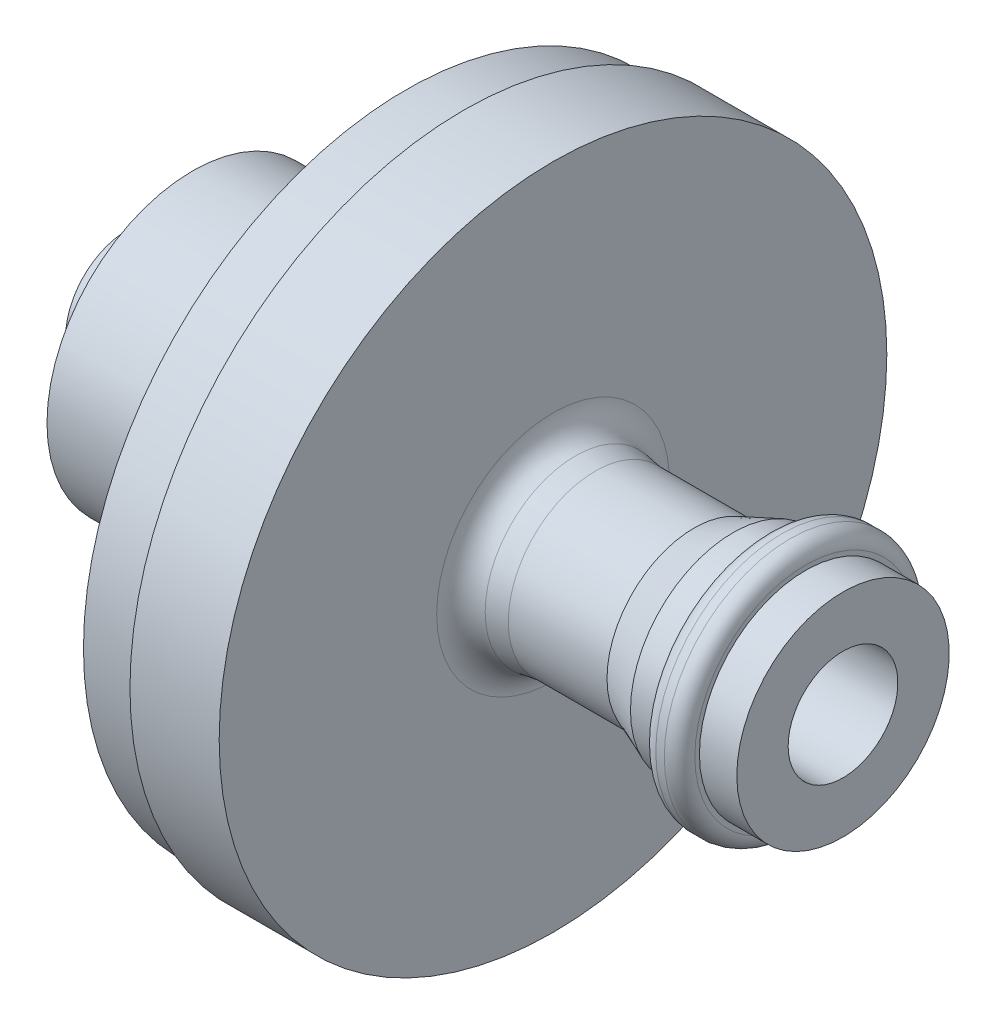
SolidWorks part; units mm, degrees
material "PE High Density"
ref_plane "Front" through (0, 0, 0) normal (0, 0, 1) x (1, 0, 0)
ref_plane "Top" through (0, 0, 0) normal (0, 1, 0) x (1, 0, 0)
ref_plane "Right" through (0, 0, 0) normal (1, 0, 0) x (0, 0, -1)
ref_axis "Axis1" through (0, 0, 55) along (0, 0, -1)
sketch "Sketch1" plane through (0, 0, 0) normal (0, 0, 1) x (1, 0, 0)
  line L0 (-11.7644, 0) -> (11.7996, 0) construction
  line L1 (91.544, 276.0235) -> (466.2107, 276.0235) construction
  line L2 (11.6361, 1.794) -> (11.6361, 3.474)
  line L3 (9.9137, 4.1245) -> (9.6365, 4.1245)
  line L5 (8.041, 3.3568) -> (6.7615, 2.845)
  line L6 (6.7615, 2.845) -> (3.5333, 2.845)
  line L7 (3.5333, 2.845) -> (2.881, 2.9485)
  line L8 (2.15, 10.9195) -> (2.15, 3.8045)
  line L9 (2.15, 10.9195) -> (-0.7683, 10.9195)
  line L10 (-0.7683, 10.9195) -> (-0.7683, 10.5517)
  line L11 (-0.7683, 10.5517) -> (-2.6571, 10.5517)
  line L12 (-2.6571, 10.5517) -> (-2.6571, 5.7944)
  line L13 (-3.2857, 4.8659) -> (-3.361, 4.8358)
  line L14 (-3.7324, 4.7643) -> (-9.6368, 4.7643)
  line L15 (-9.6368, 4.7643) -> (-9.6368, 3.9686)
  line L16 (-9.6368, 3.9686) -> (-4.4563, 3.9686)
  line L18 (-4.4563, 2.0288) -> (-11.7644, 2.0288)
  line L19 (-11.7644, 2.0288) -> (-11.7644, 1.404)
  line L20 (-11.7644, 1.404) -> (-4.5676, 1.404)
  line L23 (4.0412, 0.397) -> (4.0412, 0.794)
  line L24 (5.0412, 1.794) -> (11.6361, 1.794)
  line L25 (8.041, 3.3568) -> (9.1365, 3.3568)
  line L26 (9.1365, 3.3568) -> (9.1365, 3.6245)
  line L27 (9.6365, 4.1245) -> (9.9137, 4.1245)
  line L28 (10.4137, 3.6245) -> (10.4137, 3.474)
  line L29 (10.4137, 3.474) -> (11.6361, 3.474)
  line L30 (-3.5676, 0.4032) -> (4.0412, 0.397)
  arc A0 (2.15, 3.8045) -> (2.881, 2.9485) centre (3.0168, 3.8045) ccw
  arc A1 (-3.4568, 2.9987) -> (-4.4563, 3.9686) centre (-4.4563, 2.9686) ccw
  arc A2 (4.0412, 0.794) -> (5.0412, 1.794) centre (5.0412, 0.794) cw
  arc A3 (-3.7324, 4.7643) -> (-3.361, 4.8358) centre (-3.7324, 5.7643) ccw
  arc A4 (-3.2857, 4.8659) -> (-2.6571, 5.7944) centre (-3.6571, 5.7944) ccw
  arc A5 (-3.4568, 2.9987) -> (-4.4563, 2.0288) centre (-4.4563, 3.0288) cw
  arc A6 (-3.5676, 0.4032) -> (-4.5676, 1.404) centre (-4.5676, 0.404) ccw
  arc A7 (9.6365, 4.1245) -> (9.1365, 3.6245) centre (9.6365, 3.6245) ccw
  arc A8 (10.4137, 3.6245) -> (9.9137, 4.1245) centre (9.9137, 3.6245) ccw
  point P5 (0, 0)
  dimension "D3" = 1
  dimension "D4" = 1
  dimension "D5" = 1
  dimension "D6" = 1
  dimension "D7" = 1
  dimension "D8" = 1
  dimension "D2" = 0.5
  dimension "D9" = 0.5
  dimension "D1" = 7.6088
revolve "Revolve4" add sketch "Sketch1" angle 360 about L0 region at (0.1451, 4.4412, 0)
